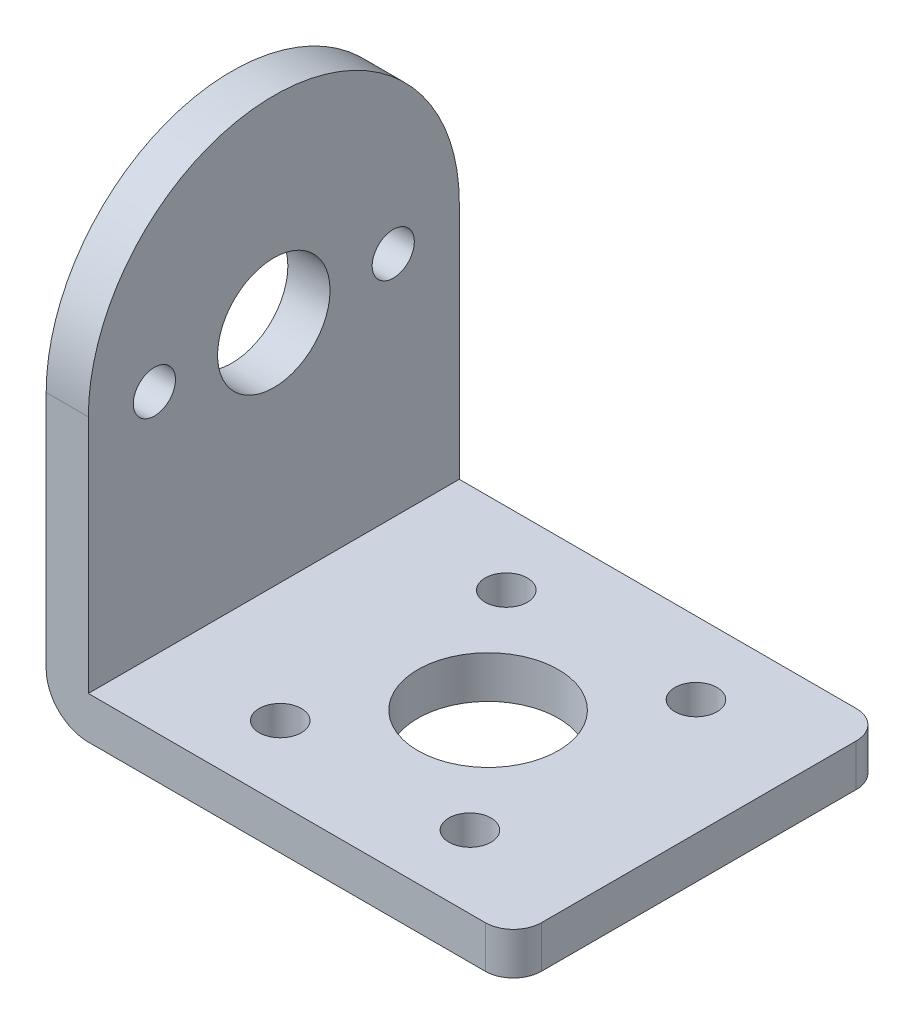
SolidWorks part; units mm, degrees
ref_plane "Front Plane" through (0, 0, 0) normal (0, 0, 1) x (1, 0, 0)
ref_plane "Top Plane" through (0, 0, 0) normal (0, 1, 0) x (1, 0, 0)
ref_plane "Right Plane" through (0, 0, 0) normal (1, 0, 0) x (0, 0, -1)
sketch "Sketch1" plane through (0, 0, 0) normal (0, 1, 0) x (1, 0, 0)
  line L0 (-13.625, 13.2) -> (-13.625, -13.2)
  line L1 (-16.625, 13.2) -> (16.625, 13.2)
  line L2 (-16.625, 13.2) -> (-16.625, -13.2)
  line L3 (-16.625, -13.2) -> (16.625, -13.2)
  line L4 (16.625, 13.2) -> (16.625, -13.2)
  line L5 (-16.625, 13.2) -> (16.625, -13.2) construction
  line L6 (-16.625, -13.2) -> (16.625, 13.2) construction
  line L7 (-13.625, -13.2) -> (-16.625, -13.2)
  line L8 (-16.625, 13.2) -> (-13.625, 13.2)
  point P0 (0, 0)
  dimension "D1" = 33.25
  dimension "D2" = 26.4
  dimension "D3" = 3
extrude "Boss-Extrude1" add sketch "Sketch1" along normal blind 3 contours L4 L1 L0 L3 region at (1.5, 0, 0)
extrude "Boss-Extrude2" add sketch "Sketch1<3>" along normal blind 33.25 contours L2 L3 L0 L1 region at (-15.125, 0, 0)
sketch "Sketch1<3>" plane through (0, 0, 0) normal (0, 1, 0) x (1, 0, 0) same geometry as "Sketch1"
fillet "Fillet1" radius 3 1 edges at (-16.625, 0, 0)
sketch "Sketch2" plane through (-13.625, 0, 0) normal (1, 0, 0) x (0, 0, -1)
  line L0 (13.2, 33.25) -> (13.2, 3) construction
  line L1 (-13.2, 20.05) -> (13.2, 20.05)
  line L2 (-13.2, 33.25) -> (-13.2, 3) construction
  line L3 (13.2, 33.25) -> (-13.2, 33.25)
  line L4 (-13.2, 33.25) -> (-13.2, 20.05)
  line L5 (13.2, 33.25) -> (-13.2, 33.25) construction
  line L6 (0, 33.25) -> (0, 14.496) construction
  line L7 (13.2, 33.25) -> (13.2, 20.05)
  arc A0 (13.2, 20.05) -> (-13.2, 20.05) centre (0, 20.05) ccw
  arc A1 (13.2, 20.05) -> (-13.2, 20.05) centre (0, 20.05) ccw
  line M4 (13.2, 3) -> (13.2, 33.25)
  line M5 (13.2, 33.25) -> (-13.2, 33.25)
  line M6 (-13.2, 33.25) -> (-13.2, 3)
  dimension "D1" = 13.2
extrude "Cut-Extrude1" cut sketch "Sketch2" against normal through all both and the other way through all contours A0 L3 M6 | A0 M4 M5 region at (-13.625, 30.3015, 10.2515) region at (-13.625, 30.3015, -10.2515)
fillet "Fillet2" radius 2 2 edges at (16.625, 1.5, -13.2) (16.625, 1.5, 13.2)
sketch "Sketch3" plane through (-13.625, 0, 0) normal (1, 0, 0) x (0, 0, -1)
  line L0 (0, 33.25) -> (18.3581, 33.25) construction
  line L1 (13.2, 20.05) -> (13.2, 3) construction
  line L2 (0, 33.25) -> (0, 5.3518) construction
  circle A0 centre (0, 19.25) radius 4
  arc A2 (13.2, 20.05) -> (-13.2, 20.05) centre (0, 20.05) ccw construction
  circle A3 centre (8.5, 19.25) radius 1.5
  circle A4 centre (-8.5, 19.25) radius 1.5
  dimension "D1" = 8
  dimension "D2" = 14
  dimension "D5" = 3
  dimension "D3" = 13.2
  dimension "D4" = 8.5
  dimension "D6" = 14
extrude "Cut-Extrude2" cut sketch "Sketch3" against normal through all
sketch "Sketch4" plane through (0, 3, 0) normal (0, 1, 0) x (1, 0, 0)
  line L0 (-13.625, 13.2) -> (14.625, 13.2) construction
  line L1 (16.625, 11.2) -> (16.625, -11.2) construction
  line L2 (-13.625, -13.2) -> (16.0392, 12.6142) construction
  line L3 (16.0392, 12.6142) -> (16.0392, -12.6142) construction
  line L4 (16.0392, -12.6142) -> (-13.625, 13.2) construction
  line L5 (-13.625, -13.2) -> (-13.625, 13.2) construction
  line L6 (-5.125, -8.0429) -> (8.375, -8.0429) construction
  line L7 (8.375, -8.0429) -> (8.375, 8.0429) construction
  line L8 (8.375, 8.0429) -> (-5.125, 8.0429) construction
  line L9 (-5.125, 8.0429) -> (-5.125, -8.0429) construction
  circle A0 centre (1.625, 0) radius 5
  arc A1 (16.625, 11.2) -> (14.625, 13.2) centre (14.625, 11.2) ccw construction
  arc A2 (14.625, -13.2) -> (16.625, -11.2) centre (14.625, -11.2) ccw construction
  circle A3 centre (-5.125, -8.0429) radius 1.5
  circle A4 centre (1.625, 0) radius 10.5
  circle A5 centre (8.375, 8.0429) radius 1.5
  circle A6 centre (8.375, -8.0429) radius 1.5
  circle A7 centre (-5.125, 8.0429) radius 1.5
  dimension "D3" = 10
  dimension "D6" = 3
  dimension "D7" = 21
  dimension "D4" = 3
  dimension "D5" = 3
  dimension "D8" = 3
  dimension "D1" = 13.2
  dimension "D2" = 15
  dimension "D9" = 13.5
extrude "Cut-Extrude3" cut sketch "Sketch4" against normal up to next contours A0 | A4 A7 | A7 | A3 | A6 | A5 region at (1.625, 3, 0) region at (-5.5216, 3, -8.5154)
